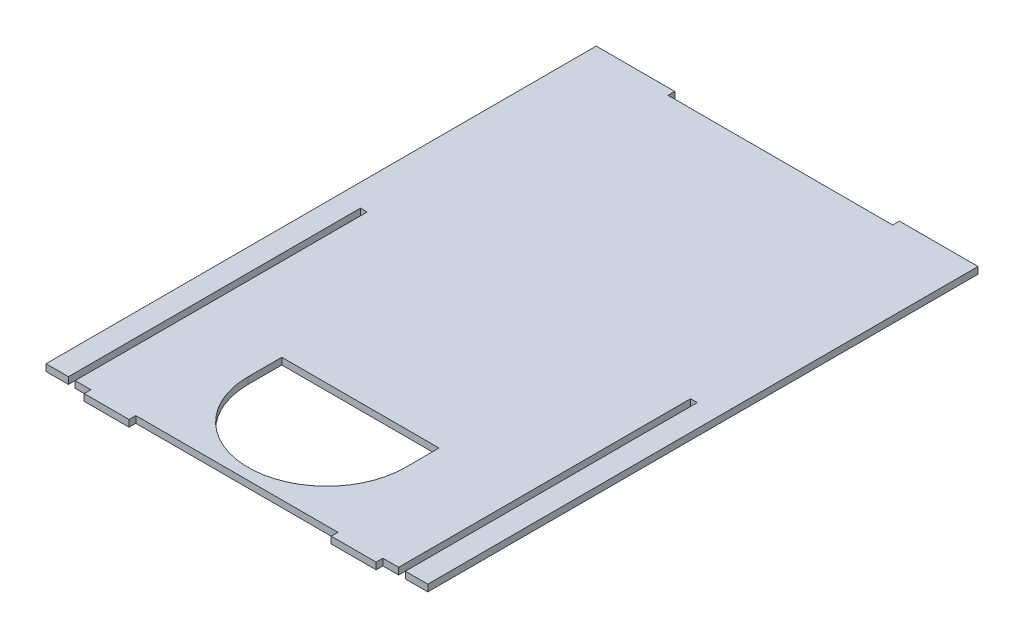
SolidWorks part; units mm, degrees
ref_plane "Front Plane" through (0, 0, 0) normal (0, 0, 1) x (1, 0, 0)
ref_plane "Top Plane" through (0, 0, 0) normal (0, 1, 0) x (1, 0, 0)
ref_plane "Right Plane" through (0, 0, 0) normal (1, 0, 0) x (0, 0, -1)
sketch "Sketch1" plane through (0, 0, 0) normal (0, 1, 0) x (1, 0, 0)
  line L0 (300, 0) -> (300, -6)
  line L2 (0, 0) -> (0, 490)
  line L3 (0, 490) -> (340, 490)
  line L4 (340, 0) -> (340, 490)
  line L5 (300, -6) -> (260, -6)
  line L6 (260, -6) -> (260, 0)
  line L7 (40, 0) -> (40, -6)
  line L8 (40, -6) -> (80, -6)
  line L9 (80, -6) -> (80, 0)
  line L10 (40, 0) -> (0, 0)
  line L11 (80, 0) -> (260, 0)
  line L12 (300, 0) -> (340, 0)
  point P11 (80, -3)
  dimension "D1" = 340
  dimension "D2" = 490
  dimension "D3" = 40
  dimension "D4" = 6
  dimension "D5" = 40
  dimension "D6" = 180
extrude "Boss-Extrude1" add sketch "Sketch1" along normal blind 6
sketch "Sketch2" plane through (0, 6, 0) normal (0, 1, 0) x (1, 0, 0)
  line L1 (20, 0) -> (26, 0)
  line L2 (20, 0) -> (20, 260)
  line L3 (20, 260) -> (26, 260)
  line L4 (26, 0) -> (26, 260)
  line L5 (0, 490) -> (0, 0) construction
  line L6 (0, 0) -> (40, 0) construction
  line L7 (0, 0) -> (40, 0) construction
  dimension "D1" = 260
  dimension "D2" = 6
  dimension "D3" = 20
extrude "Cut-Extrude1" cut sketch "Sketch2" against normal blind 6
pattern_linear "LPattern1" count 2 spacing 294 along (1, 0, 0) of "Cut-Extrude1"
sketch "Sketch3" plane through (0, 6, 0) normal (0, 1, 0) x (1, 0, 0)
  line L0 (100, 80) -> (100, 110)
  line L3 (340, 490) -> (0, 490) construction
  line L4 (70, 490) -> (270, 490)
  line L5 (70, 490) -> (70, 484)
  line L6 (70, 484) -> (270, 484)
  line L7 (270, 490) -> (270, 484)
  line L9 (240, 80) -> (240, 110)
  line L10 (100, 110) -> (240, 110)
  line L12 (0, 490) -> (0, 0) construction
  line L13 (80, 0) -> (260, 0) construction
  arc A1 (100, 80) -> (240, 80) centre (170, 80) ccw
  point P14 (170, 490)
  dimension "D1" = 200
  dimension "D2" = 70
  dimension "D3" = 80
  dimension "D4" = 170
  dimension "D6" = 140
  dimension "D5" = 6
  dimension "D8" = 30
extrude "Cut-Extrude2" cut sketch "Sketch3" against normal blind 6
